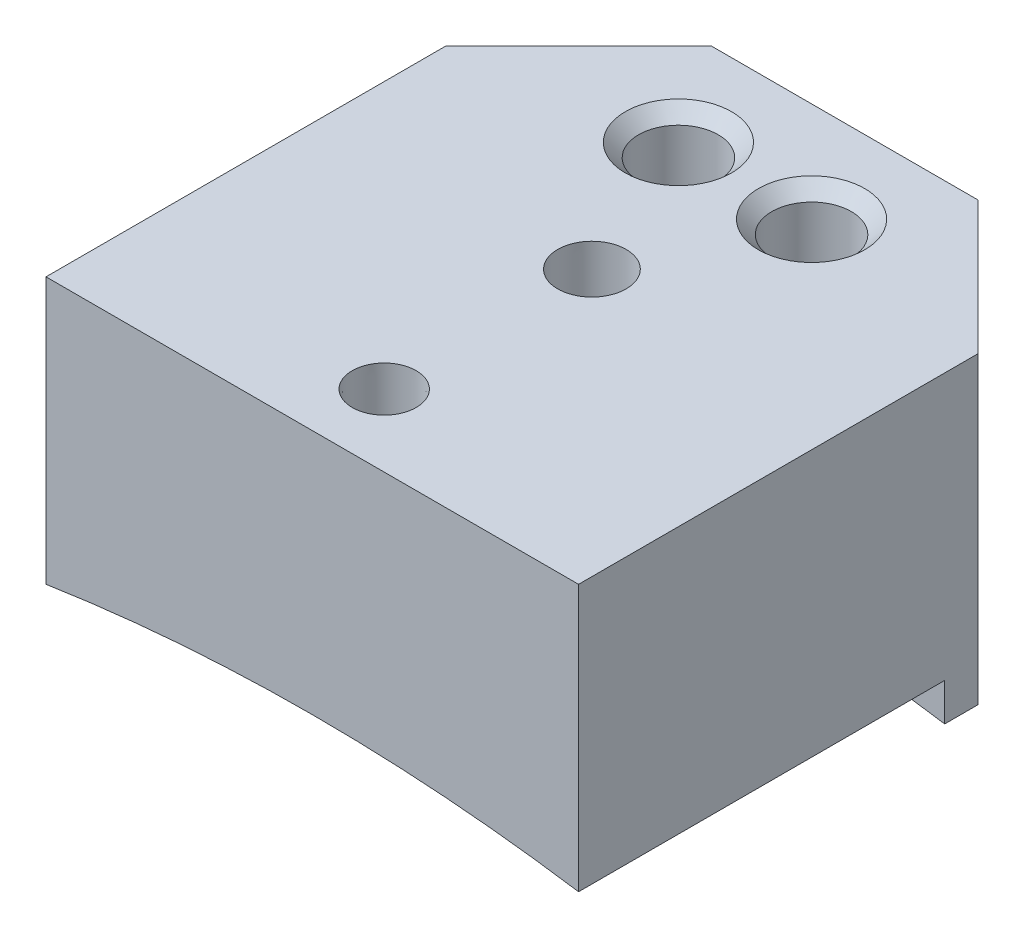
SolidWorks part; units mm, degrees
ref_plane "Front Plane" through (0, 0, 0) normal (0, 0, 1) x (1, 0, 0)
ref_plane "Top Plane" through (0, 0, 0) normal (0, 1, 0) x (1, 0, 0)
ref_plane "Right Plane" through (0, 0, 0) normal (1, 0, 0) x (0, 0, -1)
sketch "Sketch1" plane through (0, 0, 0) normal (0, 1, 0) x (1, 0, 0)
  line L0 (-28.5118, 6.4953) -> (-22.1618, 12.8453)
  line L1 (-22.1618, 12.8453) -> (-9.4618, 12.8453)
  line L2 (-28.5118, 6.4953) -> (-28.5118, -12.5547)
  line L3 (-28.5118, -12.5547) -> (-3.1118, -12.5547)
  line L4 (-3.1118, 6.4953) -> (-3.1118, -12.5547)
  line L5 (-9.4618, 12.8453) -> (-3.1118, 6.4953)
  line L6 (-15.8118, -12.5547) -> (-15.8118, 12.8453) construction
  line L8 (-3.1118, 6.4953) -> (-3.1118, 12.8453) construction
  line L9 (-3.1118, 12.8453) -> (-9.4618, 12.8453) construction
  dimension "D1" = 12.7
  dimension "D2" = 25.4
  dimension "D3" = 25.4
extrude "Boss-Extrude1" add sketch "Sketch1" along normal blind 12.7
sketch "Sketch2" plane through (0, 0, 12.5547) normal (0, 0, 1) x (1, 0, 0)
  circle A0 centre (-15.8118, -82.8523) radius 83.82
  dimension "D1" = 167.64
extrude "Cut-Extrude1" cut sketch "Sketch2" against normal through all both and the other way through all
sketch "Sketch5" plane through (0, 0, -12.8453) normal (0, 0, -1) x (-1, 0, 0)
  line L0 (3.1118, 12.7) -> (3.1118, 0) construction
  line L1 (3.1118, 12.7) -> (3.1118, 0)
  line L4 (28.5118, 12.7) -> (28.5118, 0) construction
  line L5 (28.5118, 12.7) -> (28.5118, 0)
  line L6 (28.5118, -1.7992) -> (28.5118, 0)
  line L7 (3.1118, -1.7992) -> (3.1118, 0)
  line L8 (3.1118, 12.7) -> (28.5118, 12.7)
  arc A0 (3.1118, -1.7992) -> (28.5118, -1.7992) centre (15.8118, -82.8523) cw
  arc A1 (28.5118, 0) -> (3.1118, 0) centre (15.8118, -82.8523) ccw construction
  arc A2 (28.5118, 0) -> (3.1118, 0) centre (15.8118, -82.8523) ccw construction
  dimension "D1" = 82.042
extrude "Boss-Extrude2" add sketch "Sketch5" against normal blind 7.9375
chamfer "Chamfer1" distance 6.35 angle 45 2 edges at (-28.5118, 5.4504, -12.8453) (-3.1118, 5.4504, -12.8453)
hole_wizard "#10-24 Tapped Hole1" positions "Sketch3" profile "Sketch4" tap size "#10-24" standard "ANSI Inch" end condition through all
sketch "Sketch3" plane through (0, 12.7, 0) normal (0, 1, 0) x (1, 0, 0)
  line L0 (-15.8118, 12.8453) -> (-15.8118, 3.4006) construction
  line L1 (-9.4618, 12.8453) -> (-22.1618, 12.8453) construction
  point P0 (-18.9868, 8.0828)
  point P10 (0, 0)
  point P11 (0, 0)
  point P12 (-12.6368, 8.0828)
  dimension "D1" = 4.7625
  dimension "D2" = 3.175
sketch "Sketch4" plane through (-18.9868, 12.7, -8.0828) normal (1, 0, 0) x (0, 0, 1)
  line L0 (0, 0) -> (0, 14.4992)
  line L1 (0, 14.4992) -> (1.8986, 14.4992)
  line L2 (1.8986, 14.4992) -> (1.8986, 0.635)
  line L3 (1.8986, 0.635) -> (2.5337, 0)
  line L5 (2.5337, 0) -> (0, 0)
  line L6 (-1.8986, 0.635) -> (-2.5337, 0) construction
  line L11 (0, -6.35) -> (0, 107.95) construction
  dimension "Thru Tap Drill Dia." = 3.7973
  dimension "Thru Tap Drill Depth" = 14.4992
  dimension "Near C'Sink Dia." = 5.0673
  dimension "Near C'Sink Angle" = 90
cosmetic thread "Hole Thread3" parameters "D2"=4.826
cosmetic thread "Hole Thread4" parameters "D2"=4.826
sketch "Sketch6" plane through (0, 12.7, 0) normal (0, 1, 0) x (1, 0, 0)
  spline S0 degree 3 poles (-15.9109, -10.6497) (-15.6088, -10.6497) (-15.4088, -10.6093) (-15.0421, -10.4569) (-14.8723, -10.3433) (-14.6614, -10.1321) (-14.5971, -10.0536) (-14.4867, -9.888) (-14.44, -9.8004) (-14.3254, -9.523) (-14.286, -9.3252) (-14.2863, -9.0237) (-14.2962, -8.9248) (-14.3351, -8.7299) (-14.3646, -8.633) (-14.4412, -8.4488) (-14.488, -8.3613) (-14.5989, -8.1955) (-14.6633, -8.1172) (-14.8743, -7.9067) (-15.0444, -7.7932) (-15.4113, -7.6415) (-15.6118, -7.6017) (-15.9102, -7.6018) (-16.0112, -7.6118) (-16.2064, -7.6508) (-16.3014, -7.6796) (-16.5784, -7.7944) (-16.7462, -7.9063) (-16.9595, -8.1198) (-17.0224, -8.1968) (-17.1327, -8.362) (-17.1804, -8.4512) (-17.2567, -8.6357) (-17.2855, -8.7307) (-17.3244, -8.9262) (-17.3342, -9.0271) (-17.3341, -9.3253) (-17.2941, -9.5259) (-17.142, -9.8926) (-17.0285, -10.0627) (-16.8176, -10.2736) (-16.7392, -10.3379) (-16.5735, -10.4485) (-16.486, -10.4953) (-16.3014, -10.5718) (-16.2047, -10.6011) (-16.0099, -10.6398) (-15.9109, -10.6497) (-15.6088, -10.6497) (-15.4088, -10.6093) knots -0.03125 -0.03125 0 0 0.0625 0.0625 0.125 0.125 0.15625 0.15625 0.1875 0.1875 0.25 0.25 0.28125 0.28125 0.3125 0.3125 0.34375 0.34375 0.375 0.375 0.4375 0.4375 0.5 0.5 0.53125 0.53125 0.5625 0.5625 0.625 0.625 0.65625 0.65625 0.6875 0.6875 0.71875 0.71875 0.75 0.75 0.8125 0.8125 0.875 0.875 0.90625 0.90625 0.9375 0.9375 0.96875 0.96875 1 1 1.0625 1.0625 1.125 only from (-15.8102, -10.6497) to (-15.8102, -10.6497) construction
  spline S1 degree 3 poles (-15.9109, -10.6497) (-15.6088, -10.6497) (-15.4088, -10.6093) (-15.0421, -10.4569) (-14.8723, -10.3433) (-14.6614, -10.1321) (-14.5971, -10.0536) (-14.4867, -9.888) (-14.44, -9.8004) (-14.3254, -9.523) (-14.286, -9.3252) (-14.2863, -9.0237) (-14.2962, -8.9248) (-14.3351, -8.7299) (-14.3646, -8.633) (-14.4412, -8.4488) (-14.488, -8.3613) (-14.5989, -8.1955) (-14.6633, -8.1172) (-14.8743, -7.9067) (-15.0444, -7.7932) (-15.4113, -7.6415) (-15.6118, -7.6017) (-15.9102, -7.6018) (-16.0112, -7.6118) (-16.2064, -7.6508) (-16.3014, -7.6796) (-16.5784, -7.7944) (-16.7462, -7.9063) (-16.9595, -8.1198) (-17.0224, -8.1968) (-17.1327, -8.362) (-17.1804, -8.4512) (-17.2567, -8.6357) (-17.2855, -8.7307) (-17.3244, -8.9262) (-17.3342, -9.0271) (-17.3341, -9.3253) (-17.2941, -9.5259) (-17.142, -9.8926) (-17.0285, -10.0627) (-16.8176, -10.2736) (-16.7392, -10.3379) (-16.5735, -10.4485) (-16.486, -10.4953) (-16.3014, -10.5718) (-16.2047, -10.6011) (-16.0099, -10.6398) (-15.9109, -10.6497) (-15.6088, -10.6497) (-15.4088, -10.6093) knots -0.03125 -0.03125 0 0 0.0625 0.0625 0.125 0.125 0.15625 0.15625 0.1875 0.1875 0.25 0.25 0.28125 0.28125 0.3125 0.3125 0.34375 0.34375 0.375 0.375 0.4375 0.4375 0.5 0.5 0.53125 0.53125 0.5625 0.5625 0.625 0.625 0.65625 0.65625 0.6875 0.6875 0.71875 0.71875 0.75 0.75 0.8125 0.8125 0.875 0.875 0.90625 0.90625 0.9375 0.9375 0.96875 0.96875 1 1 1.0625 1.0625 1.125 only from (-15.8102, -10.6497) to (-15.8102, -10.6497)
  spline S2 degree 3 poles (-17.442, 0.8881) (-17.442, 0.5646) (-17.3987, 0.3504) (-17.2355, -0.0422) (-17.1139, -0.2241) (-16.8877, -0.4499) (-16.8036, -0.5187) (-16.6263, -0.6369) (-16.5325, -0.687) (-16.2355, -0.8097) (-16.0236, -0.8519) (-15.7008, -0.8516) (-15.5949, -0.8409) (-15.3862, -0.7993) (-15.2825, -0.7677) (-15.0851, -0.6857) (-14.9915, -0.6355) (-14.814, -0.5168) (-14.7301, -0.4479) (-14.5047, -0.222) (-14.3832, -0.0397) (-14.2207, 0.3532) (-14.178, 0.5678) (-14.1782, 0.8874) (-14.1889, 0.9955) (-14.2306, 1.2046) (-14.2615, 1.3063) (-14.3435, 1.5041) (-14.3946, 1.5994) (-14.5128, 1.7761) (-14.5805, 1.8587) (-14.7329, 2.0109) (-14.8153, 2.0784) (-14.9922, 2.1965) (-15.0878, 2.2476) (-15.2854, 2.3293) (-15.3871, 2.3601) (-15.5964, 2.4017) (-15.7045, 2.4123) (-16.0238, 2.4121) (-16.2385, 2.3692) (-16.6313, 2.2065) (-16.8134, 2.0849) (-17.0392, 1.8591) (-17.1081, 1.7751) (-17.2266, 1.5977) (-17.2767, 1.5039) (-17.3586, 1.3063) (-17.39, 1.2027) (-17.4314, 0.9941) (-17.442, 0.8881) (-17.442, 0.5646) (-17.3987, 0.3504) knots -0.03125 -0.03125 0 0 0.0625 0.0625 0.125 0.125 0.15625 0.15625 0.1875 0.1875 0.25 0.25 0.28125 0.28125 0.3125 0.3125 0.34375 0.34375 0.375 0.375 0.4375 0.4375 0.5 0.5 0.53125 0.53125 0.5625 0.5625 0.59375 0.59375 0.625 0.625 0.65625 0.65625 0.6875 0.6875 0.71875 0.71875 0.75 0.75 0.8125 0.8125 0.875 0.875 0.90625 0.90625 0.9375 0.9375 0.96875 0.96875 1 1 1.0625 1.0625 1.125 only from (-17.442, 0.7803) to (-17.442, 0.7803) construction
  spline S3 degree 3 poles (-17.442, 0.8881) (-17.442, 0.5646) (-17.3987, 0.3504) (-17.2355, -0.0422) (-17.1139, -0.2241) (-16.8877, -0.4499) (-16.8036, -0.5187) (-16.6263, -0.6369) (-16.5325, -0.687) (-16.2355, -0.8097) (-16.0236, -0.8519) (-15.7008, -0.8516) (-15.5949, -0.8409) (-15.3862, -0.7993) (-15.2825, -0.7677) (-15.0851, -0.6857) (-14.9915, -0.6355) (-14.814, -0.5168) (-14.7301, -0.4479) (-14.5047, -0.222) (-14.3832, -0.0397) (-14.2207, 0.3532) (-14.178, 0.5678) (-14.1782, 0.8874) (-14.1889, 0.9955) (-14.2306, 1.2046) (-14.2615, 1.3063) (-14.3435, 1.5041) (-14.3946, 1.5994) (-14.5128, 1.7761) (-14.5805, 1.8587) (-14.7329, 2.0109) (-14.8153, 2.0784) (-14.9922, 2.1965) (-15.0878, 2.2476) (-15.2854, 2.3293) (-15.3871, 2.3601) (-15.5964, 2.4017) (-15.7045, 2.4123) (-16.0238, 2.4121) (-16.2385, 2.3692) (-16.6313, 2.2065) (-16.8134, 2.0849) (-17.0392, 1.8591) (-17.1081, 1.7751) (-17.2266, 1.5977) (-17.2767, 1.5039) (-17.3586, 1.3063) (-17.39, 1.2027) (-17.4314, 0.9941) (-17.442, 0.8881) (-17.442, 0.5646) (-17.3987, 0.3504) knots -0.03125 -0.03125 0 0 0.0625 0.0625 0.125 0.125 0.15625 0.15625 0.1875 0.1875 0.25 0.25 0.28125 0.28125 0.3125 0.3125 0.34375 0.34375 0.375 0.375 0.4375 0.4375 0.5 0.5 0.53125 0.53125 0.5625 0.5625 0.59375 0.59375 0.625 0.625 0.65625 0.65625 0.6875 0.6875 0.71875 0.71875 0.75 0.75 0.8125 0.8125 0.875 0.875 0.90625 0.90625 0.9375 0.9375 0.96875 0.96875 1 1 1.0625 1.0625 1.125 only from (-17.442, 0.7803) to (-17.442, 0.7803)
extrude "Cut-Extrude2" cut sketch "Sketch6" against normal through all
